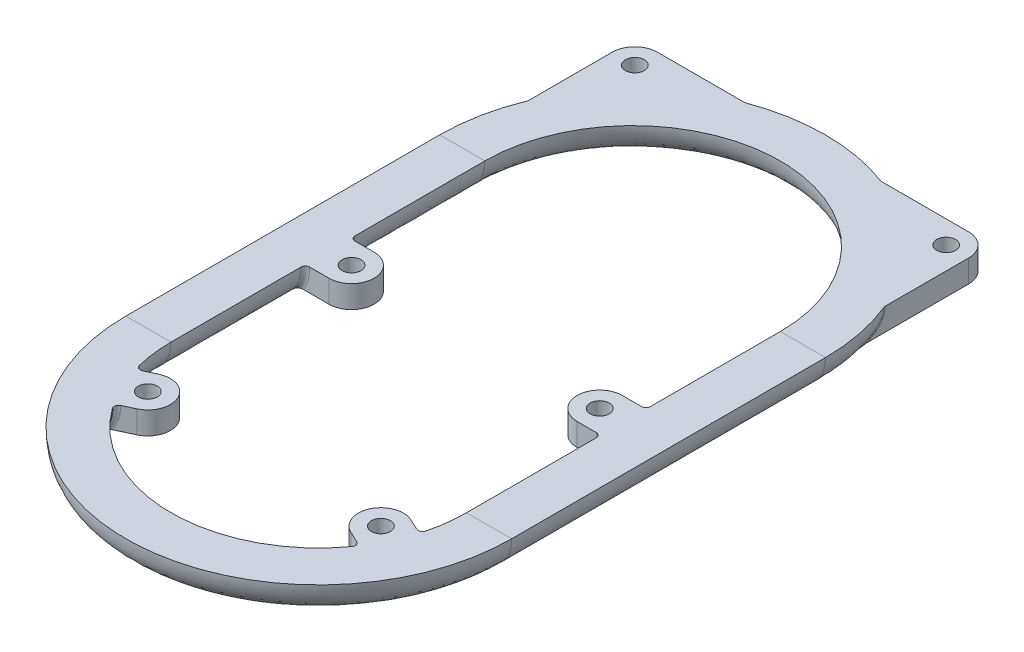
SolidWorks part; units mm, degrees
ref_plane "Front Plane" through (0, 0, 0) normal (0, 0, 1) x (1, 0, 0)
ref_plane "Top Plane" through (0, 0, 0) normal (0, 1, 0) x (1, 0, 0)
ref_plane "Right Plane" through (0, 0, 0) normal (1, 0, 0) x (0, 0, -1)
sketch "Sketch1" plane through (0, 0, 0) normal (0, 1, 0) x (1, 0, 0)
  line L0 (-37.5, -69.5691) -> (-37.5, 0)
  line L1 (37.5, -69.5691) -> (37.5, 0)
  arc A0 (37.5, 0) -> (-37.5, 0) centre (0, 0) ccw
  arc A1 (-37.5, -69.5691) -> (37.5, -69.5691) centre (0, -69.5691) ccw
  dimension "D2" = 75
  dimension "D5" = 37.5
  dimension "D4" = 69.5691
  dimension "D6" = 69.5691
sketch "Sketch2" plane through (0, 0, 0) normal (0, 0, 1) x (1, 0, 0)
  line L0 (39.5, 0) -> (36, 0)
  line L1 (38.5, -3.5) -> (38.5, -5)
  line L2 (38.5, -3.5) -> (39.5, -3.5)
  line L3 (39.5, -3.5) -> (39.5, 0)
  line L4 (42.75, 1.4783) -> (32.75, 1.4783)
  line L5 (36, -3.5) -> (36, 0)
  line L6 (37, -3.5) -> (36, -3.5)
  line L8 (37, -3.5) -> (37, -5)
  line L10 (37.75, 1.4783) -> (37.75, -7.9806) construction
  spline S0 degree 2 poles (38.5, -5) (42.5898, -3.9003) (42.75, 1.4783) knots 0 0 0 0.917744 0.917744 0.917744
  spline S1 degree 2 poles (37, -5) (32.9102, -3.9003) (32.75, 1.4783) knots 0 0 0 0.917744 0.917744 0.917744
  point P9 (37.75, 1.4783)
  point P12 (37.75, 0)
  point P18 (37.75, 1.4783)
  dimension "D2" = 37.75
  dimension "D4" = 0.75
  dimension "D5" = 5
  dimension "D6" = 1.5
  dimension "D10" = 1
  dimension "D11" = 3.5
  dimension "D12" = 5
sweep "Sweep1" add profiles "Sketch2" path "Sketch1"
sketch "Sketch4" plane through (0, 0, 0) normal (0, 1, 0) x (1, 0, 0)
  line L0 (-39.5, 35) -> (-39.5, 11.0939)
  line L1 (-34.5, 40) -> (-9.1282, 40)
  line L3 (0, 0) -> (0, 55.51) construction
  line L4 (34.5, 40) -> (9.1282, 40)
  line L5 (39.5, 35) -> (39.5, 11.0939)
  circle A0 centre (-34.5, 35) radius 2.1
  arc A1 (-34.5, 40) -> (-39.5, 35) centre (-34.5, 35) ccw
  arc A2 (-9.1282, 40) -> (-39.5, 11.0939) centre (0, 0) ccw
  arc A3 (9.1282, 40) -> (39.5, 11.0939) centre (0, 0) cw
  arc A4 (34.5, 40) -> (39.5, 35) centre (34.5, 35) cw
  circle A5 centre (34.5, 35) radius 2.1
  dimension "D1" = 10
  dimension "D2" = 4.2
  dimension "D3" = 4.2
extrude "Boss-Extrude1" add sketch "Sketch4" along normal up to surface (1.4783 mm away) and the other way offset from surface 5 up to face at (0, 1.4783, -18.875) other way up to face at (0, 1.4783, -18.875)
fillet "Fillet1" radius 1 6 edges at (-39.5, -1.3996, -15.1017) (-13.7921, -1.3305, -40) (13.8797, -1.2395, -40) (39.5, -1.1416, -15.326) (28.3205, -3.5217, -29.7356) (-28.3205, -3.5217, -29.7356)
sketch "Sketch5" plane through (0, 0, 0) normal (0, 1, 0) x (1, 0, 0)
  line L0 (-33.5, -69.5691) -> (-33.5, 0) construction
  line L1 (-27.5, -39.7846) -> (-35.5, -39.7846)
  line L2 (-35.5, -39.7846) -> (-35.5, -29.7846)
  line L3 (-35.5, -29.7846) -> (-27.5, -29.7846)
  line L4 (-37.5, -69.5691) -> (-37.5, 0) construction
  line L5 (0, 33.5) -> (0, -124.3262) construction
  line L6 (35.5, -29.7846) -> (27.5, -29.7846)
  line L7 (35.5, -39.7846) -> (35.5, -29.7846)
  line L8 (27.5, -39.7846) -> (35.5, -39.7846)
  circle A0 centre (-27.5, -34.7846) radius 2.1
  arc A1 (-27.5, -39.7846) -> (-27.5, -29.7846) centre (-27.5, -34.7846) ccw
  arc A3 (27.5, -39.7846) -> (27.5, -29.7846) centre (27.5, -34.7846) cw
  circle A4 centre (27.5, -34.7846) radius 2.1
  dimension "D1" = 4.2
  dimension "D2" = 6
  dimension "D3" = 10
  dimension "D4" = 2
extrude "Boss-Extrude2" add sketch "Sketch5" along normal up to surface (1.4783 mm away) and the other way offset from surface 5 up to face at (-37.75, 1.4783, 34.7846) other way up to face at (-37.75, 1.4783, 34.7846)
fillet "Fillet3" radius 1 6 edges at (-33.3993, -1.8991, 39.7846) (-34.4359, -3.5217, 34.7846) (-33.4476, -2.0105, 29.7846) (33.4476, -2.0105, 39.7846) (34.4359, -3.5217, 34.7846) (33.3993, -1.8991, 29.7846)
sketch "Sketch6" plane through (0, 0, 0) normal (0, 1, 0) x (1, 0, 0)
  line L0 (-33.5, -69.5691) -> (33.5, -69.5691) construction
  line L1 (0, -69.5691) -> (-31.7208, -84.3608) construction
  line L2 (0, -69.5691) -> (31.7208, -84.3608) construction
  line L3 (-31.7208, -84.3608) -> (-25.8298, -81.6138) construction
  line L4 (-33.5085, -79.6775) -> (-27.9429, -77.0822)
  line L5 (-29.2823, -88.7406) -> (-23.7167, -86.1453)
  line L6 (31.7208, -84.3608) -> (25.8298, -81.6138) construction
  line L7 (29.2823, -88.7406) -> (23.7167, -86.1453)
  line L8 (33.5085, -79.6775) -> (27.9429, -77.0822)
  line L9 (-73.2967, -103.7479) -> (-76.3245, -105.1598) construction
  circle A0 centre (-25.8298, -81.6138) radius 2.1
  arc A1 (-33.5, -69.5691) -> (33.5, -69.5691) centre (0, -69.5691) ccw construction
  circle A2 centre (25.8298, -81.6138) radius 2.1
  arc A4 (27.9429, -77.0822) -> (23.7167, -86.1453) centre (25.8298, -81.6138) ccw
  arc A6 (-23.7167, -86.1453) -> (-27.9429, -77.0822) centre (-25.8298, -81.6138) ccw
  arc A7 (29.2823, -88.7406) -> (33.5085, -79.6775) centre (0, -69.5691) ccw
  arc A8 (-33.5085, -79.6775) -> (-29.2823, -88.7406) centre (0, -69.5691) ccw
  point P15 (40.8287, -88.6079)
  point P17 (-47.2975, -91.6243)
  dimension "D4" = 4.2
  dimension "D5" = 4.2
  dimension "D6" = 5
  dimension "D7" = 5
  dimension "D9" = 70
  dimension "D1" = 25
  dimension "D2" = 25
  dimension "D3" = 28.5
  dimension "D8" = 28.5
extrude "Boss-Extrude3" add sketch "Sketch6" along normal up to surface (1.4783 mm away) and the other way offset from surface 5 up to face at (0, 1.4783, 88.4441) other way up to face at (0, 1.4783, 88.4441)
fillet "Fillet4" radius 1 6 edges at (-27.8196, -1.9088, 88.0585) (-31.2095, -3.5217, 84.1224) (-32.0714, -1.9736, 79.0074) (27.8452, -1.9736, 88.0704) (31.2095, -3.5217, 84.1224) (32.0458, -1.9088, 78.9954)
equation "\"D2@Sketch6\"=\"D1@Sketch6\""
equation "\"D3@Sketch6\"=67/2-5"
equation "\"D8@Sketch6\"=\"D3@Sketch6\""
